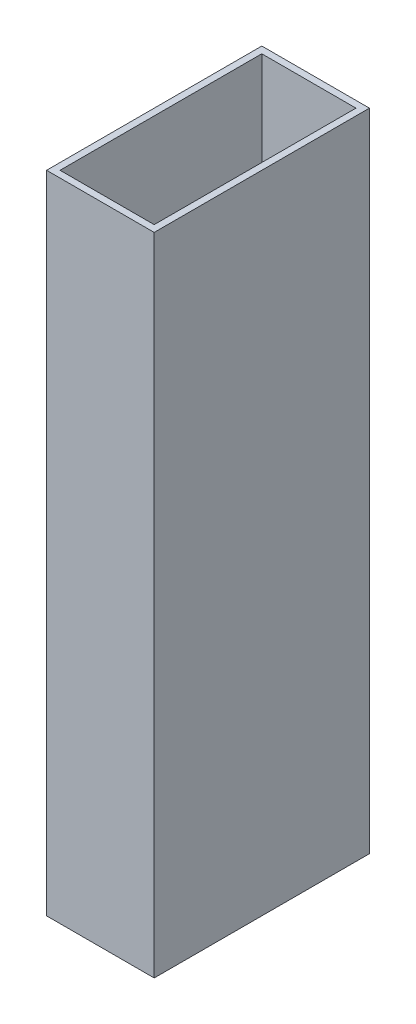
SolidWorks part; units mm, degrees
material "6061-T6 (SS)"
ref_plane "Front" through (0, 0, 0) normal (0, 0, 1) x (1, 0, 0)
ref_plane "Top" through (0, 0, 0) normal (0, 1, 0) x (1, 0, 0)
ref_plane "Right" through (0, 0, 0) normal (1, 0, 0) x (0, 0, -1)
sketch "Sketch1" plane through (0, 0, 0) normal (0, 1, 0) x (1, 0, 0)
  line L1 (12.7, 25.4) -> (-12.7, 25.4)
  line L2 (12.7, 25.4) -> (12.7, -25.4)
  line L3 (12.7, -25.4) -> (-12.7, -25.4)
  line L4 (-12.7, 25.4) -> (-12.7, -25.4)
  line L5 (12.7, 25.4) -> (-12.7, -25.4) construction
  line L6 (12.7, -25.4) -> (-12.7, 25.4) construction
  point P0 (0, 0)
  dimension "D1" = 25.4
  dimension "D2" = 50.8
extrude "Extrude-Thin1" add sketch "Sketch1" along normal up to surface (152.4 mm away) thin thin type one direction reverse wall 1.5875
